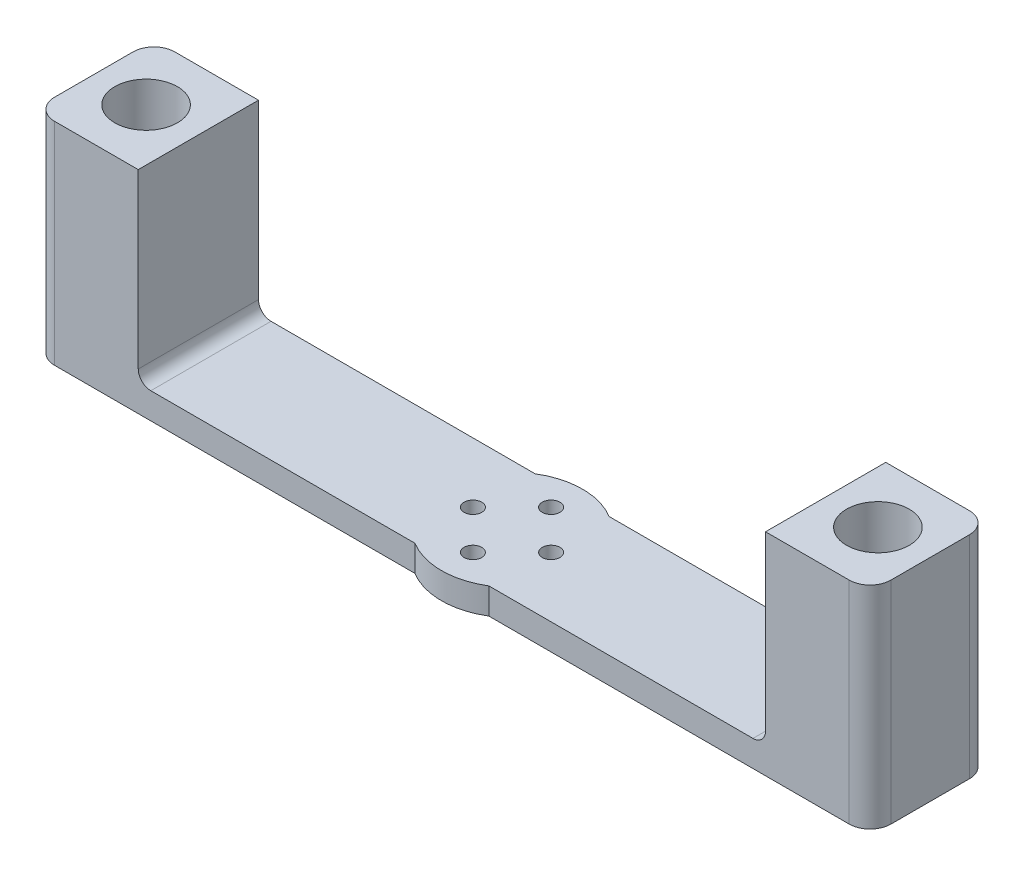
SolidWorks part; units mm, degrees
ref_plane "Front Plane" through (0, 0, 0) normal (0, 0, 1) x (1, 0, 0)
ref_plane "Top Plane" through (0, 0, 0) normal (0, 1, 0) x (1, 0, 0)
ref_plane "Right Plane" through (0, 0, 0) normal (1, 0, 0) x (0, 0, -1)
sketch "Sketch1" plane through (0, 0, 0) normal (0, 1, 0) x (1, 0, 0)
  line L0 (0, 0) -> (0, 4.9523) construction
  line L1 (0, 4.9523) -> (0, 0) construction
  line L2 (0, 0) -> (2.8355, 0) construction
  circle A0 centre (0, 0) radius 17.145
  circle A2 centre (0, 9.5) radius 2.15
  circle A3 centre (9.5, 0) radius 2.15
  circle A4 centre (0, -9.5) radius 2.15
  circle A5 centre (-9.5, 0) radius 2.15
  dimension "D2" = 34.29
  dimension "D3" = 4.3
extrude "Boss-Extrude1" add sketch "Sketch1" along normal blind 6.35
sketch "Sketch2" plane through (0, 6.35, 0) normal (0, 1, 0) x (1, 0, 0)
  line L1 (-96.52, -14.605) -> (96.52, -14.605)
  line L2 (-101.6, -9.525) -> (-101.6, 9.525)
  line L3 (-96.52, 14.605) -> (96.52, 14.605)
  line L4 (101.6, -9.525) -> (101.6, 9.525)
  line L5 (-101.6, -14.605) -> (101.6, 14.605) construction
  line L6 (-101.6, 14.605) -> (101.6, -14.605) construction
  circle A0 centre (-88.9, 0) radius 7.62
  circle A1 centre (88.9, 0) radius 7.62
  arc A3 (96.52, 14.605) -> (101.6, 9.525) centre (96.52, 9.525) cw
  arc A4 (96.52, -14.605) -> (101.6, -9.525) centre (96.52, -9.525) ccw
  arc A5 (-96.52, -14.605) -> (-101.6, -9.525) centre (-96.52, -9.525) cw
  arc A6 (-101.6, 9.525) -> (-96.52, 14.605) centre (-96.52, 9.525) cw
  circle A7 centre (9.5, 0) radius 2.15 construction
  circle A8 centre (0, 9.5) radius 2.15 construction
  circle A9 centre (-9.5, 0) radius 2.15 construction
  circle A10 centre (0, -9.5) radius 2.15 construction
  circle A11 centre (9.5, 0) radius 2.15
  circle A12 centre (0, 9.5) radius 2.15
  circle A13 centre (-9.5, 0) radius 2.15
  circle A14 centre (0, -9.5) radius 2.15
  point P0 (0, 0)
  dimension "D2" = 15.24
  dimension "D3" = 15.24
  dimension "D8" = 5.08
  dimension "D1" = 29.21
  dimension "D4" = 88.9
  dimension "D6" = 12.7
  dimension "D7" = 12.7
extrude "Boss-Extrude2" add sketch "Sketch2" along normal blind 45 and the other way through all
sketch "Sketch5" plane through (0, 0, -14.605) normal (0, 0, -1) x (-1, 0, 0)
  line L0 (-101.6, 0) -> (-101.6, 51.35)
  line L1 (-101.6, 51.35) -> (-76.2, 51.35)
  line L2 (-96.52, 51.35) -> (96.52, 51.35) construction
  line L3 (-76.2, 51.35) -> (-76.2, 6.35)
  line L4 (-76.2, 6.35) -> (76.2, 6.35)
  line L5 (0, 6.35) -> (0, 0)
  line L6 (101.6, 0) -> (-101.6, 0)
  line L7 (76.2, 51.35) -> (76.2, 6.35)
  line L8 (101.6, 51.35) -> (76.2, 51.35)
  line L9 (101.6, 0) -> (101.6, 51.35)
  line M8 (96.52, 51.35) -> (-96.52, 51.35)
  dimension "D1" = 25.4
  dimension "D2" = 6.35
extrude "Cut-Extrude2" cut sketch "Sketch5" against normal through all contours L7 L3 L4 M8 region at (0, 28.85, -14.605)
sketch "Sketch6" plane through (0, 0, 0) normal (0, -1, 0) x (1, 0, 0)
  circle A0 centre (-88.9, 0) radius 8.89
  circle A1 centre (-88.9, 0) radius 4.445
  circle A2 centre (88.9, 0) radius 8.89
  circle A3 centre (88.9, 0) radius 4.445
  dimension "D1" = 8.89
  dimension "D2" = 8.89
extrude "Boss-Extrude3" add sketch "Sketch6" against normal blind 4.572
fillet "Fillet2" radius 3.048 2 edges at (76.2, 6.35, 0) (-76.2, 6.35, 0)
